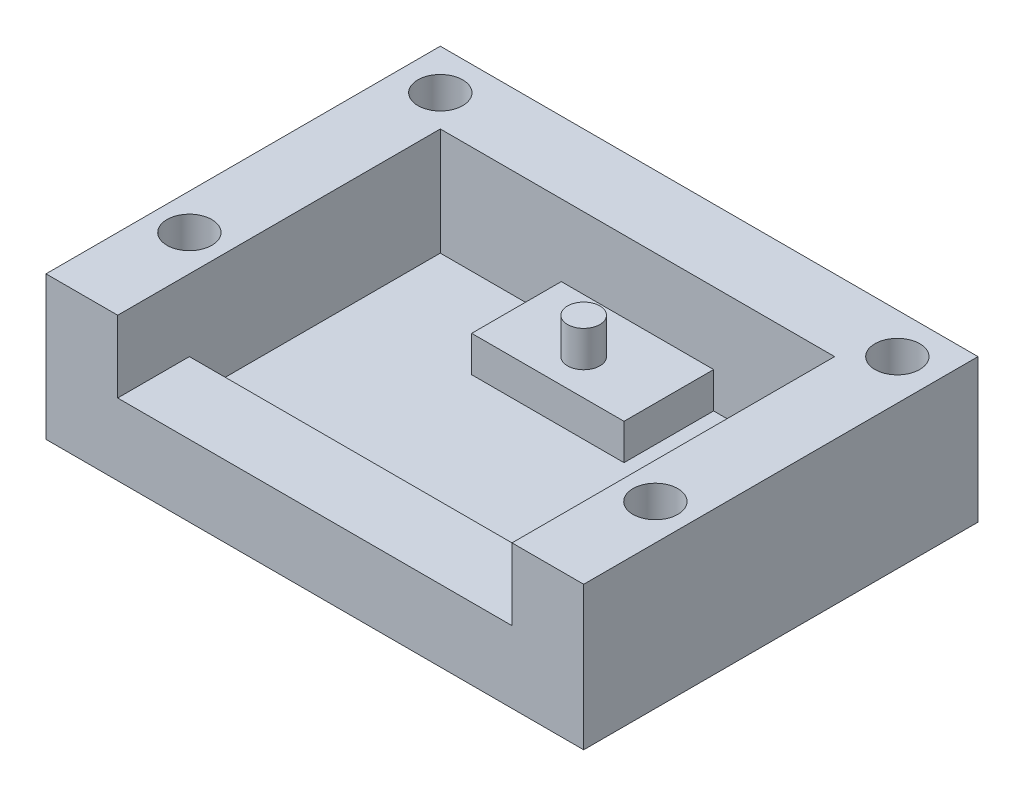
SolidWorks part; units mm, degrees
ref_plane "Plan de face" through (0, 0, 0) normal (0, 0, 1) x (1, 0, 0)
ref_plane "Plan de dessus" through (0, 0, 0) normal (0, 1, 0) x (1, 0, 0)
ref_plane "Plan de droite" through (0, 0, 0) normal (1, 0, 0) x (0, 0, -1)
sketch "Esquisse3" plane through (0, 0, 0) normal (0, 1, 0) x (1, 0, 0)
  line L1 (0, 0) -> (-30, 0)
  line L2 (0, 0) -> (0, -22)
  line L3 (0, -22) -> (-30, -22)
  line L4 (-30, 0) -> (-30, -22)
  dimension "D1" = 30
  dimension "D2" = 22
extrude "Boss.-Extru.1" add sketch "Esquisse3" along normal blind 8
sketch "Esquisse4" plane through (0, 8, 0) normal (0, 1, 0) x (1, 0, 0)
  line L8 (-4, -18) -> (-4, -4)
  line L9 (-4, -4) -> (-26, -4)
  line L10 (-26, -4) -> (-26, -18)
  line L11 (-26, -18) -> (-4, -18)
  line L12 (-4, -18) -> (-4, -4)
  line L13 (-4, -4) -> (-26, -4)
  line L14 (-26, -4) -> (-26, -18)
  line L15 (-26, -18) -> (-4, -18)
  dimension "D1" = 4
extrude "Enlèv. mat.-Extru.1" cut sketch "Esquisse4" against normal blind 6
sketch "Esquisse5" plane through (0, 8, 0) normal (0, 1, 0) x (1, 0, 0)
  line L0 (-30, -22) -> (0, -22) construction
  line L1 (-26, -18) -> (-4, -18)
  line L2 (-26, -18) -> (-26, -22)
  line L3 (-26, -22) -> (-4, -22)
  line L4 (-4, -18) -> (-4, -22)
  dimension "D1" = 22
extrude "Enlèv. mat.-Extru.2" cut sketch "Esquisse5" against normal blind 4
sketch "Esquisse7" plane through (0, 2, 0) normal (0, 1, 0) x (1, 0, 0)
  line L0 (-15, -22) -> (-15, -7) construction
  line L1 (-26, -22) -> (-4, -22) construction
  circle A1 centre (-15, -7) radius 0.9
  dimension "D2" = 1.8
  dimension "D1" = 15
extrude "Boss.-Extru.2" add sketch "Esquisse7" along normal blind 4
sketch "Esquisse9" plane through (0, 8, 0) normal (0, 1, 0) x (1, 0, 0)
  line L0 (0, 0) -> (-30, 0) construction
  line L2 (-30, 0) -> (-30, -22) construction
  circle A1 centre (-27.75, -2.25) radius 1.25
  dimension "D3" = 2.5
  dimension "D1" = 2.25
  dimension "D2" = 2.25
extrude "Enlèv. mat.-Extru.3" cut sketch "Esquisse9" against normal blind 2
ref_plane "coupe orthogonale par rapport a x" through (-15, 0, 0) normal (-1, 0, 0) x (0, 0, 1)
mirror "Symétrie1" about plane through (-15, 0, 0) normal (-1, 0, 0) of "Enlèv. mat.-Extru.3"
ref_plane "coupe orthogonale par rapport a z" through (0, 0, 11) normal (0, 0, -1) x (-1, 0, 0)
sketch "Esquisse11" plane through (0, 8, 0) normal (0, 1, 0) x (1, 0, 0)
  line L0 (-30, 0) -> (-30, -22) construction
  line L1 (-30, -22) -> (-26, -22) construction
  circle A0 centre (-28, -16) radius 1.25
  dimension "D1" = 2.5
  dimension "D2" = 2
  dimension "D3" = 6
extrude "Enlèv. mat.-Extru.4" cut sketch "Esquisse11" against normal blind 2
mirror "Symétrie2" about plane through (-15, 0, 0) normal (-1, 0, 0) of "Enlèv. mat.-Extru.4"
sketch "Esquisse12" plane through (0, 2, 0) normal (0, 1, 0) x (1, 0, 0)
  line L0 (-4, -4) -> (-26, -4) construction
  line L1 (-19.25, -4) -> (-10.75, -4)
  line L2 (-19.25, -4) -> (-19.25, -9)
  line L3 (-19.25, -9) -> (-10.75, -9)
  line L4 (-10.75, -4) -> (-10.75, -9)
  line L5 (-26, -4) -> (-26, -22) construction
  line L6 (-4, -22) -> (-4, -4) construction
  dimension "D1" = 5
  dimension "D2" = 6.75
  dimension "D3" = 6.75
extrude "Boss.-Extru.3" add sketch "Esquisse12" along normal blind 2
